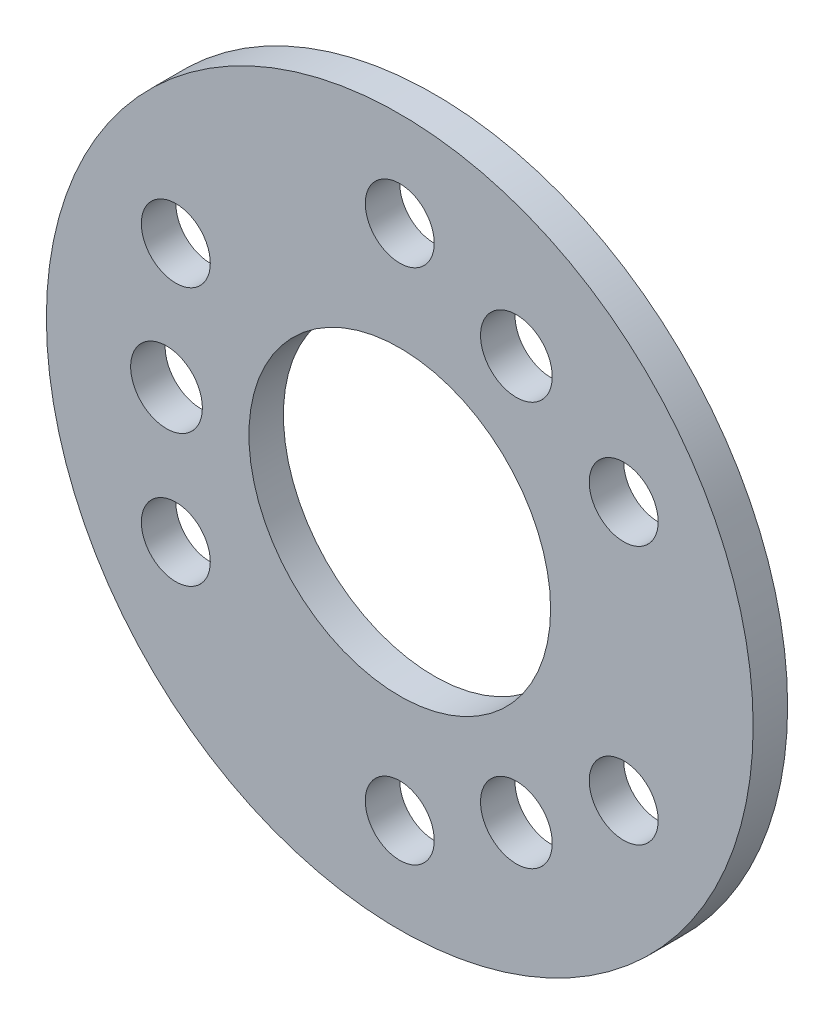
SolidWorks part; units mm, degrees
ref_plane "前视基准面" through (0, 0, 0) normal (0, 0, 1) x (1, 0, 0)
ref_plane "上视基准面" through (0, 0, 0) normal (0, 1, 0) x (1, 0, 0)
ref_plane "右视基准面" through (0, 0, 0) normal (1, 0, 0) x (0, 0, -1)
sketch "草图1" plane through (0, 0, 0) normal (0, 0, 1) x (1, 0, 0)
  line L0 (-0.9852, 0.129) -> (-0.9852, -3.2208) construction
  circle A0 centre (-0.9852, 0.129) radius 15 construction
  circle A1 centre (-0.9852, 0.129) radius 13.53 construction
  circle A2 centre (-0.9852, -14.871) radius 2
  circle A3 centre (-13.9756, -7.371) radius 2
  circle A4 centre (-13.9756, 7.629) radius 2
  circle A5 centre (-0.9852, 15.129) radius 2
  circle A6 centre (12.0052, 7.629) radius 2
  circle A7 centre (12.0052, -7.371) radius 2
  circle A8 centre (-14.5152, 0.129) radius 2.08
  circle A9 centre (5.7798, 11.8463) radius 2.08
  circle A10 centre (5.7798, -11.5883) radius 2.08
  circle A11 centre (-0.9852, 0.129) radius 8.75
  circle A12 centre (-0.9852, 0.129) radius 20.5
extrude "凸台-拉伸1" add sketch "草图1" along normal blind 2
sketch "草图2" plane through (0, 0, 0) normal (0, 0, -1) x (-1, 0, 0)
  line L0 (0.9852, 0.129) -> (0.9852, -8.621) construction
  circle A0 centre (0.9852, 0.129) radius 8.75 construction
sketch "草图3" plane through (0, 0, 0) normal (0, 0, -1) x (-1, 0, 0)
  circle A0 centre (0.9852, 0.129) radius 5
sketch "草图4" plane through (0, 0, 2) normal (0, 0, 1) x (1, 0, 0)
  circle A1 centre (-0.9852, 0.129) radius 5
